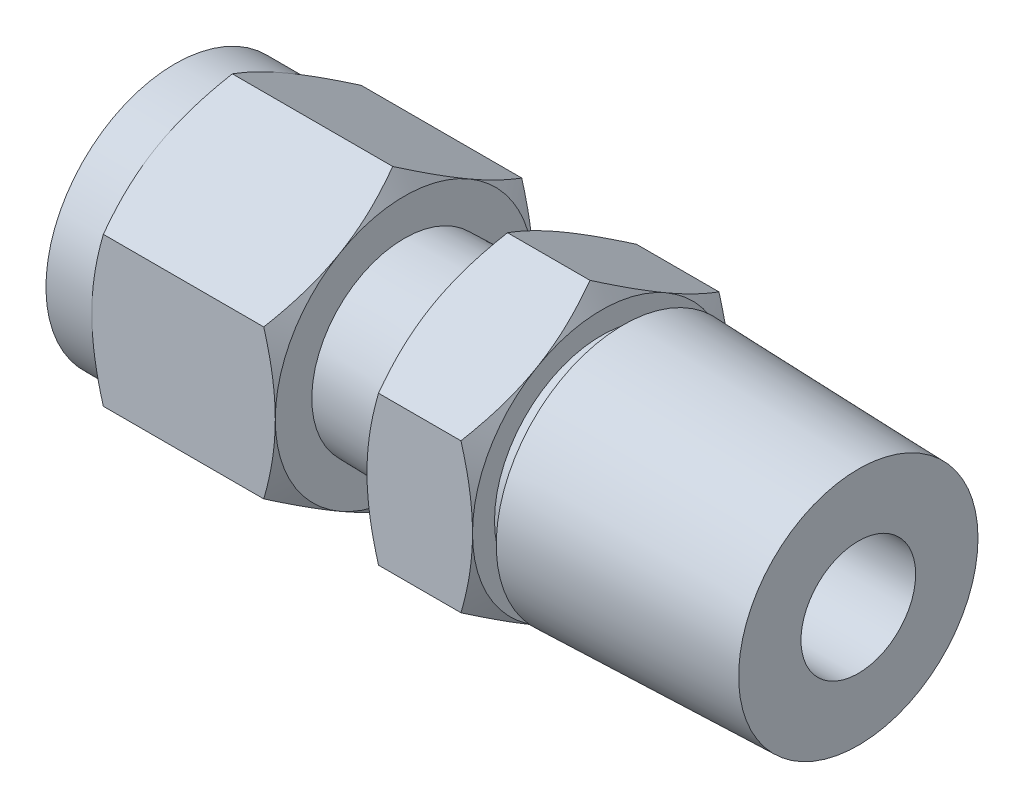
SolidWorks part; units mm, degrees
material "Brass"
ref_plane "Front Plane" through (0, 0, 0) normal (0, 0, 1) x (1, 0, 0)
ref_plane "Top Plane" through (0, 0, 0) normal (0, 1, 0) x (1, 0, 0)
ref_plane "Right Plane" through (0, 0, 0) normal (1, 0, 0) x (0, 0, -1)
sketch "Sketch5" plane through (0, 0, 0) normal (0, 0, 1) x (1, 0, 0)
  line L0 (0, 0) -> (-7.7637, 0) construction
  line L1 (-7.3838, -3.175) -> (-7.3838, -2.921)
  line L2 (-7.3838, -2.921) -> (-14.224, -2.921)
  line L5 (-13.02, -7.0333) -> (0, -6.6286)
  line L6 (0, -6.6286) -> (0, -3.175)
  line L8 (-13.6602, -5.9246) -> (-13.02, -7.0333)
  line L10 (-14.224, -5.9246) -> (-13.6602, -5.9246)
  line L12 (-14.224, -2.921) -> (-14.224, -5.9246)
  line L16 (0, -3.175) -> (-7.3838, -3.175)
  dimension "D2" = 0.254
  dimension "pipe-a" = 13.02
  dimension "pipe-b" = 14.224
  dimension "pipe thread dia" = 14.0665
  dimension "D7" = 120
  dimension "pipe-neck down" = 11.8491
  dimension "mate ref dist" = 7.3838
revolve "Revolve1" add sketch "Sketch5" angle 360 about L0
cosmetic thread "Cosmetic Thread1" parameters "D2"=14.6721
sketch "Sketch16" plane through (-14.224, 0, 0) normal (-1, 0, 0) x (0, 0, 1)
  line L1 (0, 8.2489) -> (-7.1438, 4.1244)
  line L2 (-7.1438, 4.1244) -> (-7.1438, -4.1244)
  line L3 (-7.1438, -4.1244) -> (0, -8.2489)
  line L4 (0, -8.2489) -> (7.1438, -4.1244)
  line L5 (7.1438, -4.1244) -> (7.1437, 4.1244)
  line L6 (7.1437, 4.1244) -> (0, 8.2489)
  circle A0 centre (0, 0) radius 7.1438 construction
  circle A1 centre (0, 0) radius 2.921 construction
  circle A2 centre (0, 0) radius 2.921
  dimension "pipe hex" = 14.2875
extrude "Extrude6" add sketch "Sketch16" along normal blind 5.842
sketch "Sketch17" plane through (-20.066, 0, 0) normal (-1, 0, 0) x (0, 0, 1)
  line L0 (7.1437, 4.1244) -> (0, 8.2489) construction
  circle A0 centre (0, 0) radius 7.1438
extrude "Extrude7" cut sketch "Sketch17" against normal blind 6.35 draft 60 flip side to cut
sketch "Sketch18" plane through (-14.224, 0, 0) normal (1, 0, 0) x (0, 0, -1)
  line L0 (-7.1437, 4.1244) -> (0, 8.2489) construction
  circle A0 centre (0, 0) radius 7.1438
extrude "Extrude8" cut sketch "Sketch18" against normal blind 6.35 draft 60 flip side to cut
ref_plane "Plane2" through (-25.146, 0, 0) normal (1, 0, 0) x (0, 0, -1)
sketch "Sketch6" plane through (-25.146, 0, 0) normal (1, 0, 0) x (0, 0, -1)
  line L1 (0, -8.2489) -> (7.1438, -4.1244)
  line L2 (7.1438, -4.1244) -> (7.1437, 4.1244)
  line L3 (7.1437, 4.1244) -> (0, 8.2489)
  line L4 (0, 8.2489) -> (-7.1438, 4.1244)
  line L5 (-7.1438, 4.1244) -> (-7.1438, -4.1244)
  line L6 (-7.1438, -4.1244) -> (0, -8.2489)
  circle A0 centre (0, 0) radius 7.1438 construction
  circle A1 centre (0, 0) radius 2.921 construction
  circle A2 centre (0, 0) radius 2.921
  dimension "tube hex" = 14.2875
extrude "Extrude1" add sketch "Sketch6" against normal blind 10.16
sketch "Sketch8" plane through (-35.306, 0, 0) normal (-1, 0, 0) x (0, 0, 1)
  line L0 (0, 8.2489) -> (7.1438, 4.1244) construction
  circle A0 centre (0, 0) radius 7.1437
extrude "Extrude2" cut sketch "Sketch8" against normal blind 1.524 draft 60 flip side to cut
sketch "Sketch9" plane through (-25.146, 0, 0) normal (1, 0, 0) x (0, 0, -1)
  line L0 (0, 8.2489) -> (-7.1438, 4.1244) construction
  circle A0 centre (0, 0) radius 7.1437
extrude "Extrude3" cut sketch "Sketch9" against normal blind 6.35 draft 60 flip side to cut
sketch "Sketch11" plane through (0, 0, 0) normal (0, 0, 1) x (1, 0, 0)
  line L0 (-25.146, 2.921) -> (-35.306, 2.921) construction
  line L2 (-20.955, 4.4983) -> (-21.3817, 5.2375)
  line L3 (-14.224, 4.4983) -> (-20.955, 4.4983)
  line L4 (0, -6.6286) -> (0, 6.6286) construction
  line L5 (-21.3817, 5.2375) -> (-30.226, 4.9626)
  line L6 (-14.224, -5.9246) -> (-14.224, 5.9245) construction
  line L7 (-30.226, 8.2489) -> (-30.226, 7.2099) construction
  line L8 (-37.846, 2.921) -> (-14.224, 2.921)
  line L9 (-34.6679, 8.2489) -> (-25.7841, 8.2489) construction
  line L11 (-30.226, 7.1437) -> (-37.846, 7.1437)
  line L12 (-30.226, 7.1437) -> (-30.226, 4.9626)
  line L13 (-37.846, 7.1437) -> (-37.846, 2.921)
  line L14 (-14.224, 4.4983) -> (-14.224, 2.921)
  line L17 (0, 0) -> (-14.224, 0) construction
  dimension "tube-dia" = 14.2875
  dimension "OAL" = 37.846
  dimension "D6" = 120
  dimension "tube-neck down" = 8.9967
  dimension "tube-c" = 16.4643
  dimension "tube taper dia" = 10.475
revolve "Revolve2" add sketch "Sketch11" angle 360 about L17
sketch "Sketch15" plane through (-37.846, 0, 0) normal (-1, 0, 0) x (0, 0, 1)
  circle A0 centre (0, 0) radius 3.175
extrude "Extrude5" cut sketch "Sketch15" against normal blind 15.24
sketch "Sketch19" plane through (-14.224, 0, 0) normal (1, 0, 0) x (0, 0, -1)
  point P0 (0, 0)
other "RPoint1"
other "CPoint1" parameters "Diameter"=6.35, "StubLength"=23.8125
ref_axis "Axis1" through (-32.606, 0, 0) along (1, 0, 0)
ref_axis "Axis of Rotation" through (-13.02, 0, 0) along (1, 0, 0)
